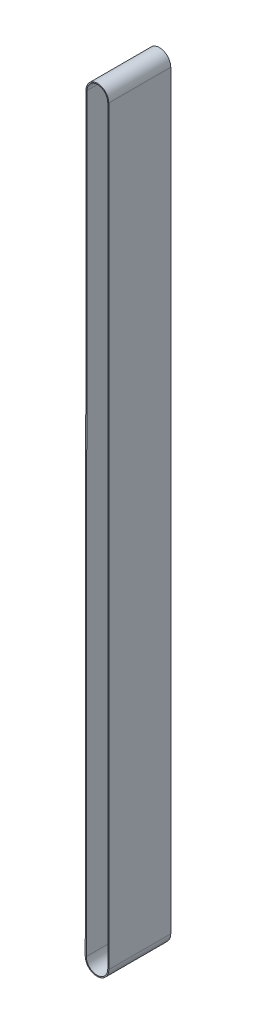
SolidWorks part; units mm, degrees
ref_plane "Front Plane" through (0, 0, 0) normal (0, 0, 1) x (1, 0, 0)
ref_plane "Top Plane" through (0, 0, 0) normal (0, 1, 0) x (1, 0, 0)
ref_plane "Right Plane" through (0, 0, 0) normal (1, 0, 0) x (0, 0, -1)
sketch "Sketch1" plane through (0, 0, 0) normal (0, 0, 1) x (1, 0, 0)
  line L0 (-96, 3595) -> (-103.9999, -3669.8855)
  line L1 (104, -3670) -> (104, 3595)
  circle A0 centre (4, 3595) radius 100 construction
  arc A1 (104, 3595) -> (-96, 3595) centre (4, 3595) ccw
  arc A5 (-103.9999, -3669.8855) -> (104, -3670) centre (0, -3670) ccw
  point P4 (0, -3905)
  point P5 (0, -3670)
extrude "Extrude-Thin3" add sketch "Sketch1" along normal mid plane 600 thin thin type one direction wall 10
